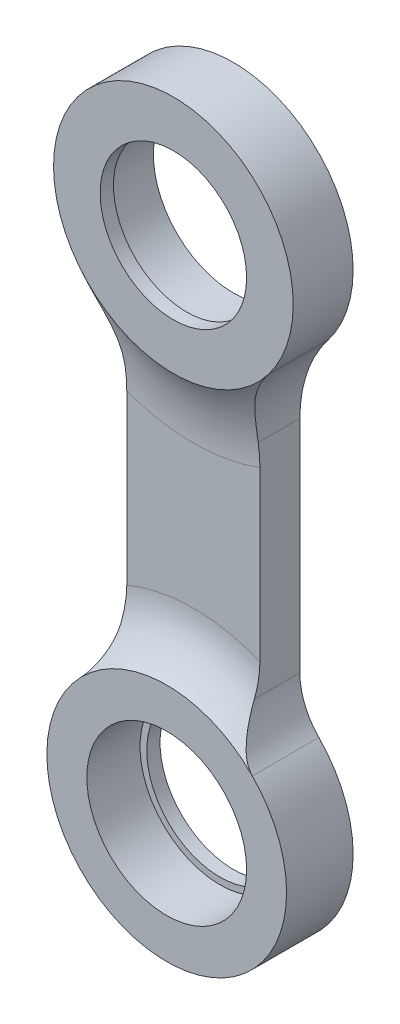
SolidWorks part; units mm, degrees
ref_plane "前视基准面" through (0, 0, 0) normal (0, 0, 1) x (1, 0, 0)
ref_plane "上视基准面" through (0, 0, 0) normal (0, 1, 0) x (1, 0, 0)
ref_plane "右视基准面" through (0, 0, 0) normal (1, 0, 0) x (0, 0, -1)
sketch "草图3" plane through (0, 0, 0) normal (0, 0, 1) x (1, 0, 0)
  line L0 (5, -7.4833) -> (-5, -7.4833) construction
  line L2 (-5, -7.4833) -> (-5, -38)
  line L3 (-5, -38) -> (5, -38)
  line L4 (5, -7.4833) -> (5, -38)
  circle A0 centre (0, 0) radius 6
  arc A2 (5, -7.4833) -> (-5, -7.4833) centre (0, 0) ccw
  dimension "D1" = 12
  dimension "D2" = 10
  dimension "D4" = 9
  dimension "D3" = 38
extrude "凸台-拉伸4" add sketch "草图3" along normal blind 3
sketch "草图5" plane through (0, 0, 0) normal (0, 0, -1) x (-1, 0, 0)
  line L0 (5, -38) -> (-5, -38) construction
  circle A0 centre (0, -38) radius 9
  dimension "D1" = 18
extrude "凸台-拉伸6" add sketch "草图5" against normal blind 5 contours A0
sketch "草图8" plane through (0, 0, 5) normal (0, 0, 1) x (1, 0, 0)
  circle A0 centre (0, -38) radius 5.5
  dimension "D1" = 11
extrude "切除-拉伸4" cut sketch "草图8" against normal through all
fillet "圆角1" radius 5 2 edges at (-5, -30.5167, 1.5) (5, -30.5167, 1.5)
fillet "圆角2" radius 5 1 edges at (0, -29, 3)
sketch "草图10" plane through (0, 0, 5) normal (0, 0, 1) x (1, 0, 0)
  circle A0 centre (0, -38) radius 6
  dimension "D1" = 12
extrude "切除-拉伸5" cut sketch "草图10" against normal blind 4
sketch "草图11" plane through (0, 0, 3) normal (0, 0, 1) x (1, 0, 0)
  circle A0 centre (0, 0) radius 6
  circle A1 centre (0, 0) radius 9
  dimension "D1" = 12
  dimension "D2" = 18
extrude "凸台-拉伸7" add sketch "草图11" along normal blind 1.5
sketch "草图12" plane through (0, 0, 4.5) normal (0, 0, 1) x (1, 0, 0)
  circle A0 centre (0, 0) radius 6 construction
  circle A1 centre (0, 0) radius 5.5
  circle A2 centre (0, 0) radius 6
  dimension "D1" = 11
extrude "凸台-拉伸8" add sketch "草图12" against normal blind 1
fillet "圆角3" radius 10 3 edges at (0, -9, 3) (-5, -7.4833, 1.5) (5, -7.4833, 1.5)
